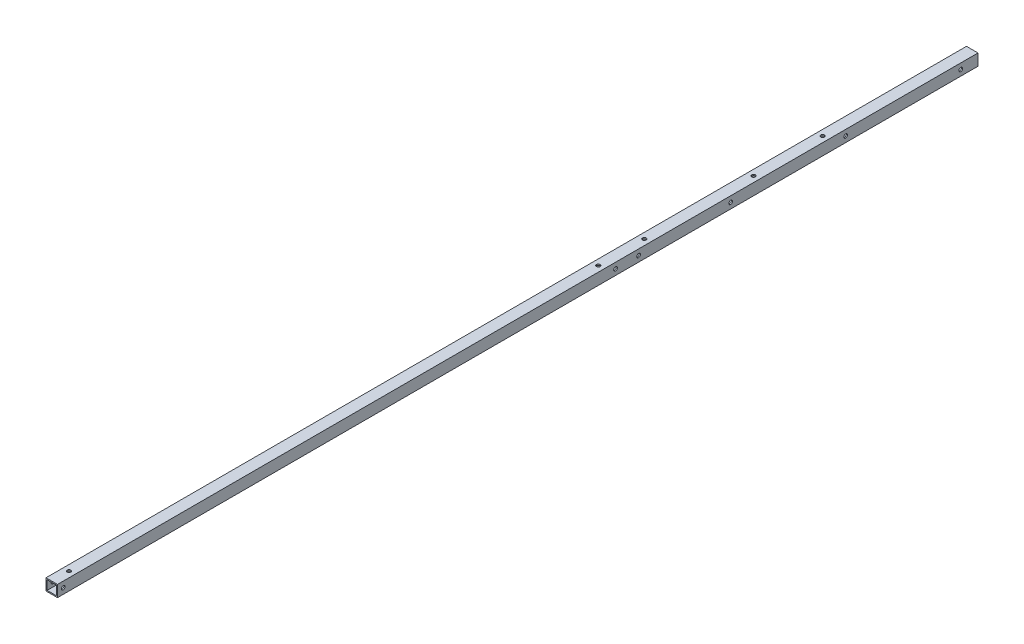
SolidWorks part; units mm, degrees
ref_plane "正面" through (0, 0, 0) normal (0, 0, 1) x (1, 0, 0)
ref_plane "平面" through (0, 0, 0) normal (0, 1, 0) x (1, 0, 0)
ref_plane "右側面" through (0, 0, 0) normal (1, 0, 0) x (0, 0, -1)
sketch "ｽｹｯﾁ1" plane through (0, 0, 0) normal (0, 0, 1) x (1, 0, 0)
  line L1 (-5, -5) -> (5, -5)
  line L2 (-5, -5) -> (-5, 5)
  line L3 (-5, 5) -> (5, 5)
  line L4 (5, -5) -> (5, 5)
  line L5 (-5, -5) -> (5, 5) construction
  line L6 (-5, 5) -> (5, -5) construction
  line L7 (-4, -4) -> (4, -4)
  line L8 (-4, -4) -> (-4, 4)
  line L9 (-4, 4) -> (4, 4)
  line L10 (4, -4) -> (4, 4)
  line L11 (-4, -4) -> (4, 4) construction
  line L12 (-4, 4) -> (4, -4) construction
  point P0 (0, 0)
  point P6 (0, 0)
  dimension "D1" = 1
  dimension "D2" = 10
  dimension "D3" = 10
extrude "ﾎﾞｽ - 押し出し1" add sketch "ｽｹｯﾁ1" along normal blind 800
sketch "ｽｹｯﾁ3" plane through (0, 5, 0) normal (0, 1, 0) x (1, 0, 0)
  line L0 (5, -800) -> (-5, -800) construction
  line L1 (-5, -800) -> (-5, 0) construction
  line L2 (5, -800) -> (5, 0) construction
  line L3 (-5, -800) -> (-5, 0) construction
  circle A0 centre (0, -785) radius 1.6
  circle A1 centre (0, -190) radius 1.6
  circle A2 centre (0, -130) radius 1.6
  circle A3 centre (0, -325) radius 1.6
  circle A4 centre (0, -285) radius 1.6
  point P18 (0, -800)
  dimension "D1" = 3.2
  dimension "D2" = 15
  dimension "D3" = 5
  dimension "D4" = 3.2
  dimension "D5" = 3.2
  dimension "D6" = 5
  dimension "D7" = 5
  dimension "D8" = 610
  dimension "D9" = 60
  dimension "D10" = 3.2
  dimension "D11" = 5
  dimension "D12" = 5
  dimension "D13" = 3.2
  dimension "D14" = 40
  dimension "D15" = 515
extrude "ｶｯﾄ - 押し出し2" cut sketch "ｽｹｯﾁ3" against normal through all
sketch "ｽｹｯﾁ4" plane through (-5, 0, 0) normal (-1, 0, 0) x (0, 0, 1)
  line L0 (800, 5) -> (800, -5) construction
  line L2 (800, 5) -> (0, 5) construction
  circle A0 centre (795, 0) radius 1.6
  circle A1 centre (295, 0) radius 1.6
  dimension "D1" = 3.2
  dimension "D2" = 5
  dimension "D3" = 5
  dimension "D4" = 3.2
  dimension "D5" = 500
  dimension "D6" = 5
extrude "ｶｯﾄ - 押し出し3" cut sketch "ｽｹｯﾁ4" against normal through all
sketch "ｽｹｯﾁ5" plane through (5, 0, 0) normal (1, 0, 0) x (0, 0, -1)
  line L0 (0, -5) -> (0, 5) construction
  line L1 (-800, 5) -> (0, 5) construction
  circle A0 centre (-15, 0) radius 1.6
  dimension "D1" = 15
  dimension "D2" = 3.2
  dimension "D3" = 5
extrude "ｶｯﾄ - 押し出し4" cut sketch "ｽｹｯﾁ5" against normal through all
pattern_linear "直線ﾊﾟﾀｰﾝ1" count 4 spacing 100 along (0, 0, 1) of "ｶｯﾄ - 押し出し4"
sketch "ｽｹｯﾁ7" plane through (5, 0, 0) normal (1, 0, 0) x (0, 0, -1)
  line L0 (-800, -5) -> (0, -5) construction
  line L1 (0, 5) -> (-110, 5)
  line L2 (0, 5) -> (0, -5)
  line L3 (0, -5) -> (-110, -5)
  line L4 (-110, 5) -> (-110, -5)
  circle A0 centre (-115, 0) radius 1.6 construction
  dimension "D1" = 5
extrude "ｶｯﾄ - 押し出し5" [suppressed] cut sketch "ｽｹｯﾁ7" against normal blind 10
